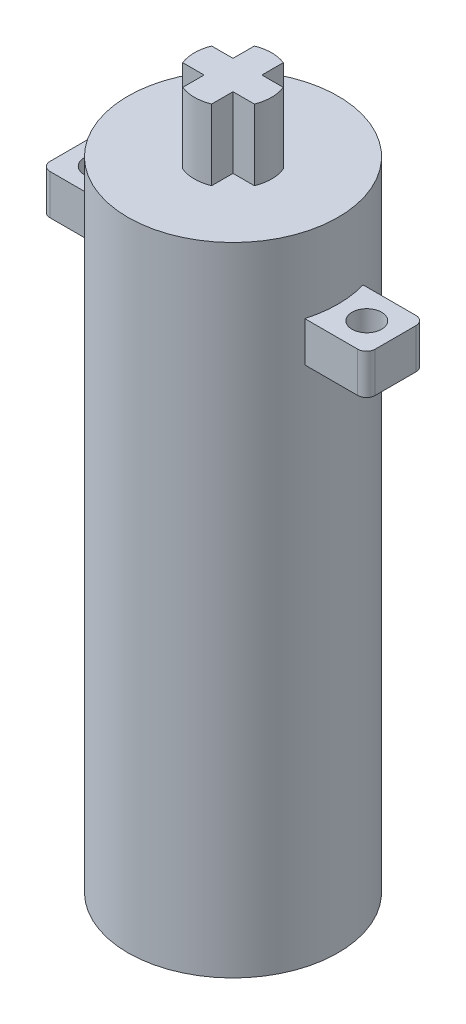
SolidWorks part; units mm, degrees
material "Plain Carbon Steel"
ref_plane "Front Plane" through (0, 0, 0) normal (0, 0, 1) x (1, 0, 0)
ref_plane "Top Plane" through (0, 0, 0) normal (0, 1, 0) x (1, 0, 0)
ref_plane "Right Plane" through (0, 0, 0) normal (1, 0, 0) x (0, 0, -1)
sketch "VigorSketch" plane through (0, 0, 0) normal (0, 1, 0) x (1, 0, 0)
  line L0 (0, -1.665) -> (0, 1.665)
  line L1 (-8.785, 1.665) -> (8.785, 1.665)
  line L2 (-9.285, 1.165) -> (-9.285, -1.165)
  line L3 (-8.785, -1.665) -> (8.785, -1.665)
  line L4 (9.285, 1.165) -> (9.285, -1.165)
  line L5 (2.0449, 0.8249) -> (0.8249, 0.8249)
  line L6 (0.8249, 0.8249) -> (0.8249, 2.0449)
  line L7 (-0.8249, 2.0449) -> (-0.8249, 0.8249)
  line L8 (-0.8249, 0.8249) -> (-2.0449, 0.8249)
  line L9 (-2.0449, -0.8249) -> (-0.8249, -0.8249)
  line L10 (-0.8249, -0.8249) -> (-0.8249, -2.0449)
  line L11 (2.0449, -0.8249) -> (0.8249, -0.8249)
  line L12 (0.8249, -0.8249) -> (0.8249, -2.0449)
  circle A0 centre (0, 0) radius 6
  arc A1 (-8.785, -1.665) -> (-9.285, -1.165) centre (-8.785, -1.165) cw
  arc A2 (9.285, -1.165) -> (8.785, -1.665) centre (8.785, -1.165) cw
  arc A3 (9.285, 1.165) -> (8.785, 1.665) centre (8.785, 1.165) ccw
  arc A4 (-8.785, 1.665) -> (-9.285, 1.165) centre (-8.785, 1.165) ccw
  circle A5 centre (7.6425, 0) radius 0.845
  circle A6 centre (-7.6425, 0) radius 0.845
  circle A7 centre (0, 0) radius 2.205
  point P7 (-9.285, 0)
  point P8 (9.285, 0)
  point P9 (0, 1.665)
  point P10 (0, -1.665)
  point P15 (9.285, -1.665)
  point P18 (9.285, 1.665)
  point P21 (-9.285, 1.665)
  point P40 (6, 0)
  dimension "D1" = 12
  dimension "D4" = 0.5
  dimension "D5" = 1.69
  dimension "D8" = 4.41
  dimension "D2" = 18.57
  dimension "D3" = 3.33
  dimension "D6" = 1.6425
  dimension "D7" = 1.665
  dimension "D9" = 1.22
extrude "VigorFlange" add sketch "VigorSketch" along normal blind 2.29 contours L1 A4 L2 A1 L3 A0 A6 | L1 A0 L3 L0 | L3 A0 L1 L0 | L4 A3 L1 A0 L3 A2 A5 region at (-3.9418, 0, 0) region at (3.9418, 0, 0) region at (-7.2747, 0, 1.6165) region at (5.9888, 0, 0.8476)
extrude "VigorAxle" add sketch "Sketch1<7>" along normal blind 10.62 contours L11 A7 L5 L6 L1 L0 L3 L12 | L8 A7 L9 L10 L3 L0 L1 L7 | L6 A7 L7 L1 | L10 A7 L12 L3 region at (-0.8902, 0, 0) region at (0, 0, 1.911) region at (0.8902, 0, 0) region at (0, 0, -1.911)
sketch "Sketch1<7>" plane through (0, 0, 0) normal (0, 1, 0) x (1, 0, 0) same geometry as "VigorSketch"
extrude "VigorBody" add sketch "VigorSketch<8>" along normal blind 6.58 and the other way blind 29.7899 contours A7 L1 A0 | A7 L3 A0 | L9 A7 L3 L10 | L1 A7 L8 L7 | L5 A7 L1 L6 | L3 A7 L11 L12 | L12 A7 L3 | L1 A7 L6 | L7 A7 L1 | L3 A7 L10 | A7 L1 A0 L3 | A7 L3 A0 L1 | L8 A7 L9 L10 L3 L0 L1 L7 | L11 A7 L5 L6 L1 L0 L3 L12 | L6 A7 L7 L1 | L10 A7 L12 L3 region at (-0.8902, 0, 0) region at (0, 0, 1.911) region at (0.8902, 0, 0) region at (0, 0, -1.911) region at (-1.044, 0, 1.7998) region at (-1.3254, 0, 1.2025) region at (1.3254, 0, 1.2025) region at (1.044, 0, 1.7998) region at (-1.3254, 0, -1.2025) region at (-1.044, 0, -1.7998) region at (1.044, 0, -1.7998) region at (1.3254, 0, -1.2025) region at (0, 0, 3.5146) region at (-3.9418, 0, 0) region at (3.9418, 0, 0) region at (0, 0, -3.5146)
sketch "VigorSketch<8>" plane through (0, 0, 0) normal (0, 1, 0) x (1, 0, 0) same geometry as "VigorSketch"
equation "\"vigorwidth\"= 0.472441in"
equation "\"D1@VigorSketch\"=\"vigorwidth\""
equation "\"vigorflangewidth\"= 0.731102in"
equation "\"D2@VigorSketch\"=\"vigorflangewidth\""
equation "\"vigorflangelength\"= 0.131102in"
equation "\"D3@VigorSketch\"=\"vigorflangelength\""
equation "\"vigorscrewsize\"= 0.066535in"
equation "\"D5@VigorSketch\"=\"vigorscrewsize\""
equation "\"vigorholeoffsetwid\"= 0.0646653in"
equation "\"D6@VigorSketch\"=\"vigorholeoffsetwid\""
equation "\"vigorholeoffsetlen\"= 0.065551in"
equation "\"D7@VigorSketch\"= \"vigorholeoffsetlen\""
equation "\"vigorflangedepth\"= 0.0901575in"
equation "\"vigordiscdepth\"= 0.0492126in"
equation "\"vigormotordepth\"= 1.12362in"
equation "\"vigortipdepth\"= 0.259055in"
equation "\"vigoraxlewidth\"= 0.173622in"
equation "\"D8@VigorSketch\"=\"vigoraxlewidth\""
equation "\"vigorcutlen\"= 0.0480315in"
equation "\"D9@VigorSketch\"=\"vigorcutlen\""
equation "\"vigoraxledepth\"= 0.159055in"
equation "\"D1@VigorBody\"=\"vigortipdepth\""
equation "\"D2@VigorBody\"=\"vigordiscdepth\"+\"vigormotordepth\""
equation "\"D1@VigorFlange\"=\"vigorflangedepth\""
equation "\"D1@VigorAxle\"=\"vigortipdepth\"+\"vigoraxledepth\""
equation "\"CageLeftBottomEdge\"=22.11mm"
equation "\"CageLeftTopEdge\"=22.11mm"
equation "\"CageRightBottomEdge\"=21.63mm"
equation "\"CageRightTopEdge\"=21.63mm"
equation "\"CageHeight\"=86.04mm"
equation "\"CageLength\"=73.76mm"
equation "\"CageTopScrewClearance\"=10mm"
equation "\"CageBottomScrewClearance\"=25mm"
equation "\"CageLeftTopDepth\"= 11.65mm"
equation "\"CageLeftBottomDepth\"=11.11mm"
equation "\"CageLeftTopHeight\"=8.56175mm"
equation "\"CageLeftBottomHeight\"=16mm"
equation "\"CageRightTopDepth\"= 11.05mm"
equation "\"CageRightBottomDepth\"=10.58mm"
equation "\"CageRightTopHeight\"=9.6mm"
equation "\"CageRightBottomHeight\"=15.49mm"
equation "\"CageLeftTopChannelDepth\"=2.41908mm"
equation "\"CageLeftBottomChannelDepth\"=2.588mm"
equation "\"CageLeftChannelHeight\"=11.7mm"
equation "\"CageRightTopChannelDepth\"=2.32mm"
equation "\"CageRightBottomChannelDepth\"=2.318mm"
equation "\"CageRightChannelHeight\"=10mm"
equation "\"CageChanRelHeight\"=23.99mm"
equation "\"CageChanRelDepth\"=5.492mm"
equation "\"CageChamberRadius\"=16.261mm"
equation "\"CageScrewDiameter\"=4.8mm"
equation "\"CageSetScrewDiameter\"=3.5mm"
equation "\"CageAxleRadius\"=6.639mm"
equation "\"CageAxleKeyHeight\"=1.619mm"
equation "\"CageAxleKeyWidth\"=2.662mm"
equation "\"CageHoseWindowWidth\"=16.29mm"
equation "\"CageHoseWindowHeight\"=26.5mm"
equation "\"CageHoseWindow-Edge\"=8.89mm"
equation "\"CageScrew-VerticalEdge\"=5.0mm"
equation "\"CageScrew-HorizontalEdge\"=7.5mm"
equation "\"CageScrew-HoseCornerScrewEdge\"=4.45mm"
equation "\"CageAxle-BottomEdge\"=56.05mm"
equation "\"CageAxle-FrontEdge\"=46.03mm"
equation "\"CageBackSetScrew-Axle\"=40mm"
equation "\"CageFrontSetScrew-Axle\"=22mm"
equation "\"CageVelocityWindow-BackEdge\"=34.8mm"
equation "\"CageVelocityWindow-BottomEdge\"=27.55mm"
equation "\"CageVelocityWindowHeight\"=22.29mm"
equation "\"CageVelocityWindowWidth\"=12.61mm"
equation "\"TriggerSlot-BottomEdge\"=6.35mm"
equation "\"TriggerSlot-FrontEdge\"=15mm"
equation "\"TriggerSlotSize\"=6.7mm"
equation "\"TriggerRackOffset\"=.236224in"
equation "\"TriggerSlotSizeInt\"=.25in"
equation "\"MotorMountLegLength\"=.25in"
equation "\"GearOffset\"=.264907in"
equation "\"TriggerSlotSpacing\"=.25in"
equation "\"TriggerMiniSlotWidth\"=3.5mm"
equation "\"TriggerRackWidth\"=6.5mm"
equation "\"TGMGearFaceDiameter\"=24.40mm"
equation "\"TGMCylinderLength\"=15.00mm"
equation "\"TGMScrewHole-Center\"=8.70mm"
equation "\"TGMScrewHoleDiameter\"=5.04mm"
equation "\"TGMCenterHoleDiameter\"=9.50mm"
equation "\"TGMShaftCollarSideLength\"=19.00mm"
equation "\"TGMShaftCollarDockingDepth\"=7.00mm"
equation "\"whitemotordepth\"=11.27mm"
equation "\"whitemotorbackdepth\"=3.845mm"
equation "\"whitemotoraxledepth\" = 3.5mm"
equation "\"whitemotoraxleoffset\"=11.4mm"
equation "\"whitemotorwidth\"=12.07mm"
equation "\"whitemotorheight\"=16.68mm"
equation "\"whitemotorcylinderlength\" =13.04mm"
equation "\"whitemotorcylinderradius\"=3.845mm"
equation "\"whitemotorcylinderoffset\"=2.35mm"
equation "\"whitemotorcutoutlength\"=1.88mm"
equation "\"whitemotorouterrad\"=5mm"
